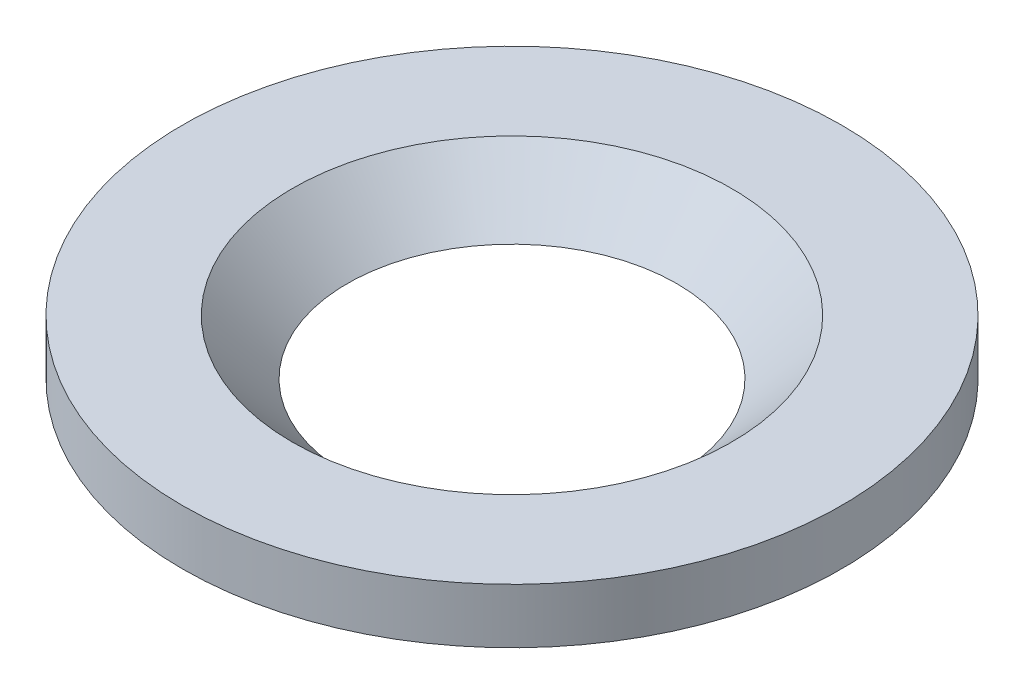
SolidWorks part; units mm, degrees
ref_plane "Front Plane" through (0, 0, 0) normal (0, 0, 1) x (1, 0, 0)
ref_plane "Top Plane" through (0, 0, 0) normal (0, 1, 0) x (1, 0, 0)
ref_plane "Right Plane" through (0, 0, 0) normal (1, 0, 0) x (0, 0, -1)
sketch "Sketch1" plane through (0, 0, 0) normal (0, 1, 0) x (1, 0, 0)
  circle A0 centre (0, 0) radius 3
  circle A1 centre (0, 0) radius 6
  dimension "D1" = 6
  dimension "D2" = 12
extrude "Boss-Extrude1" add sketch "Sketch1" along normal blind 1
chamfer "Chamfer1" distance 1 angle 45 1 edges at (0, 1, 3)
